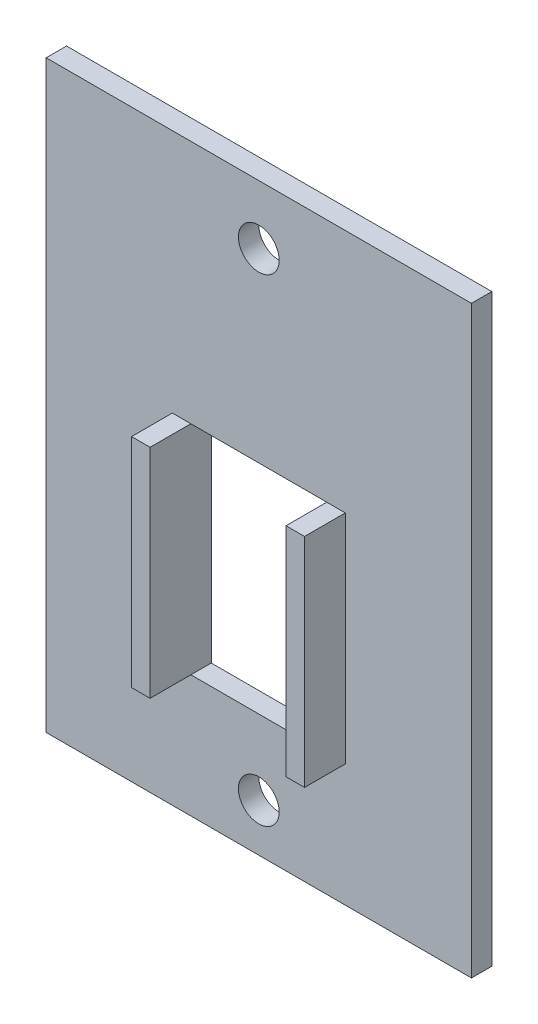
SolidWorks part; units mm, degrees
ref_plane "前视基准面" through (0, 0, 0) normal (0, 0, 1) x (1, 0, 0)
ref_plane "上视基准面" through (0, 0, 0) normal (0, 1, 0) x (1, 0, 0)
ref_plane "右视基准面" through (0, 0, 0) normal (1, 0, 0) x (0, 0, -1)
other "Configuration Table"
sketch "草图1" plane through (0, 0, 0) normal (0, 0, 1) x (1, 0, 0)
  line L0 (7.65, -9.0601) -> (-7.65, -9.0601) construction
  line L4 (15.65, 19.6129) -> (15.65, -14.6)
  line L5 (-11.65, 10.8684) -> (15.65, -14.6) construction
  line L6 (-11.65, -14.6) -> (15.65, 19.6129) construction
  line L7 (7.65, -9.0601) -> (7.65, 12.1399) construction
  line L8 (7.65, 12.1399) -> (-7.65, 12.1399) construction
  line L9 (-7.65, 12.1399) -> (-7.65, -9.0601) construction
  line L10 (0, -9.0601) -> (0, 21.7903) construction
  line L11 (5, -7.0601) -> (-5, -7.0601)
  line L12 (5, -7.0601) -> (5, 8.9399)
  line L13 (5, 8.9399) -> (-5, 8.9399)
  line L14 (-5, 8.9399) -> (-5, -7.0601)
  line L15 (15.65, 26.9399) -> (-15.65, 26.9399)
  line L16 (-15.65, 26.9399) -> (-15.65, -16.0601)
  line L17 (15.65, 26.9399) -> (15.65, 19.6129)
  line L18 (15.65, 19.6129) -> (15.65, 26.9399)
  line L19 (-15.65, -16.0601) -> (15.65, -16.0601)
  line L20 (15.65, -16.0601) -> (15.65, -14.6)
  circle A0 centre (0, -12.5601) radius 1.5
  point P0 (0, 0)
  point P21 (0, -7.0601)
  dimension "D4" = 3
  dimension "D1" = 27.3
  dimension "D3" = 2
  dimension "D5" = 10
  dimension "D6" = 16
extrude "凸台-拉伸1" add sketch "草图1" along normal blind 1.5 contours L4 A0 | L4 region at (15.1181, 2.5064, 0)
sketch "草图2" plane through (0, 0, 0) normal (0, 0, -1) x (-1, 0, 0)
  circle A0 centre (0, 22.603) radius 1.5
  dimension "D1" = 3
extrude "切除-拉伸1" cut sketch "草图2" against normal blind 10
sketch "草图3" plane through (0, 0, 1.5) normal (0, 0, 1) x (1, 0, 0)
  line L0 (0, 26.9399) -> (0, -16.0601) construction
  line L1 (5, 8.9399) -> (6.3642, 8.9399)
  line L2 (5, 8.9399) -> (5, -7.0601)
  line L3 (5, -7.0601) -> (6.3642, -7.0601)
  line L4 (6.3642, 8.9399) -> (6.3642, -7.0601)
  line L5 (15.65, 26.9399) -> (-15.65, 26.9399) construction
  line L6 (-15.65, -16.0601) -> (15.65, -16.0601) construction
  line L7 (-5, -7.0601) -> (-6.3642, -7.0601)
  line L8 (-6.3642, 8.9399) -> (-6.3642, -7.0601)
  line L9 (-5, 8.9399) -> (-6.3642, 8.9399)
  line L10 (-5, 8.9399) -> (-5, -7.0601)
extrude "凸台-拉伸2" add sketch "草图3" along normal blind 3
